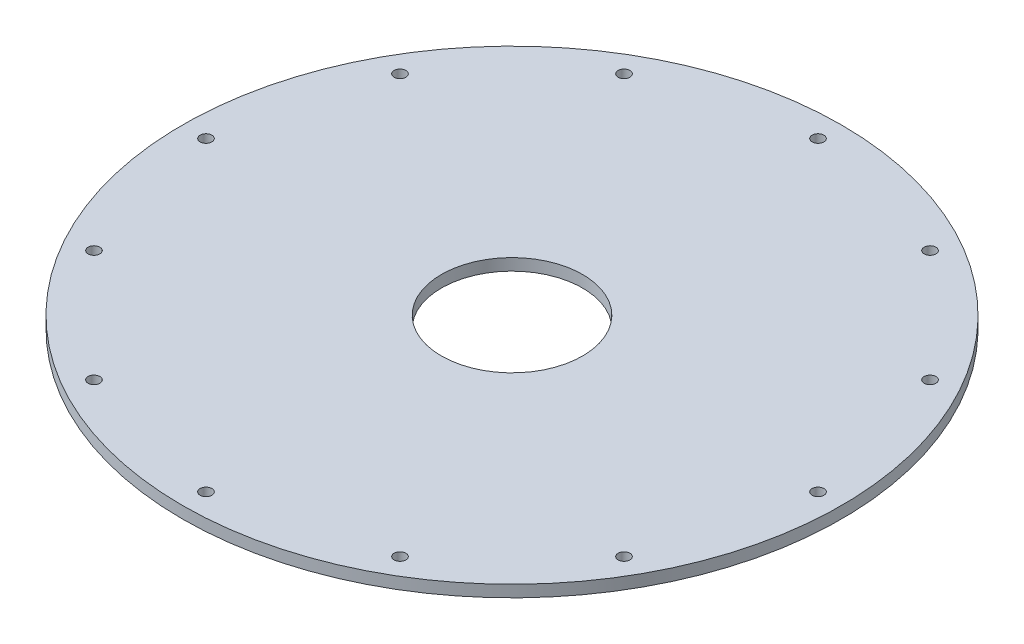
SolidWorks part; units mm, degrees
material "6063-T6"
ref_plane "Front Plane" through (0, 0, 0) normal (0, 0, 1) x (1, 0, 0)
ref_plane "Top Plane" through (0, 0, 0) normal (0, 1, 0) x (1, 0, 0)
ref_plane "Right Plane" through (0, 0, 0) normal (1, 0, 0) x (0, 0, -1)
ref_axis "Axis1" through (0, 55, 0) along (0, -1, 0)
sketch "Sketch1" plane through (0, 0, 0) normal (0, 0, 1) x (1, 0, 0)
  line L0 (-44.45, 0) -> (-9.525, 0)
  line L1 (0, 55) -> (0, -55) construction
  line L2 (-44.45, 0) -> (-44.45, 1.5875)
  line L3 (-44.45, 1.5875) -> (-9.525, 1.5875)
  line L4 (-44.45, 1.5875) -> (-9.525, 1.5875) construction
  line L5 (-9.525, 1.5875) -> (-9.525, 0)
  line L6 (-9.525, 0) -> (0, 0) construction
  line L7 (-44.45, 0) -> (-44.45, 1.5875) construction
  line L8 (-9.525, 1.5875) -> (-9.525, 0) construction
revolve "Revolve1" add sketch "Sketch1" angle 360 about axis through (0, 55, 0) along (0, -1, 0)
ref_plane "Hole Location Plane" through (0, 3.175, 0) normal (0, 1, 0) x (1, 0, 0)
sketch "Hole Location" plane through (0, 3.175, 0) normal (0, 1, 0) x (1, 0, 0)
  line L0 (0, 0) -> (-41.275, 0) construction
  circle A0 centre (0, 0) radius 41.275 construction
  dimension "D1" = 82.55
hole_wizard "1/16 (0.0625) Diameter Hole1" positions "Sketch4" profile "Sketch5" hole size "1/16" standard "ANSI Inch" end condition through all
sketch "Sketch4" plane through (0, 1.5875, 0) normal (0, 1, 0) x (1, 0, 0)
  point P0 (-41.275, 0)
sketch "Sketch5" plane through (-41.275, 1.5875, 0) normal (1, 0, 0) x (0, 0, 1)
  line L0 (0, 0) -> (0, 1.5875)
  line L1 (0, 1.5875) -> (0.7937, 1.5875)
  line L2 (0.7937, 1.5875) -> (0.7937, 0)
  line L5 (0.7937, 0) -> (0, 0)
  line L11 (0, -6.35) -> (0, 107.95) construction
  dimension "Thru Hole Dia." = 1.5875
  dimension "Thru Hole Depth" = 1.5875
pattern_circular "CirPattern1" count 12 every 30 about axis through (0, 55, 0) along (0, -1, 0) of "1/16 (0.0625) Diameter Hole1"
equation "\"D1@Hole Location\"= \"TANK DIAMETER@Cryo Tank.Assembly\"+\"GASKET SEAT THICKNESS@Cryo Tank.Assembly\""
